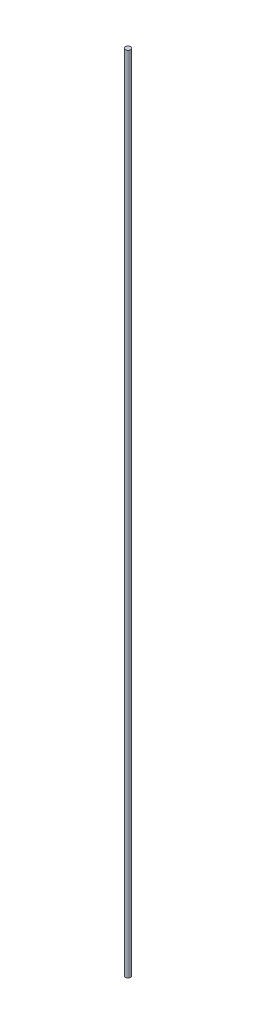
SolidWorks part; units mm, degrees
ref_plane "Спереди" through (0, 0, 0) normal (0, 0, 1) x (1, 0, 0)
ref_plane "Сверху" through (0, 0, 0) normal (0, 1, 0) x (1, 0, 0)
ref_plane "Справа" through (0, 0, 0) normal (1, 0, 0) x (0, 0, -1)
sketch "Эскиз2" plane through (0, 0, 0) normal (0, 0, 1) x (1, 0, 0)
  line L5 (-2.5, 380) -> (0, 380)
  line L6 (-2.5, 380) -> (-2.5, -380)
  line L7 (-2.5, -380) -> (0, -380)
  line L8 (0, 380) -> (0, -380)
  line L9 (-2.5, 380) -> (0, -380) construction
  line L10 (-2.5, -380) -> (0, 380) construction
  point P0 (-1.25, 0)
  point P5 (0, 0)
  dimension "D1" = 2.5
  dimension "D2" = 760
revolve "Повернуть1" add sketch "Эскиз2" angle 360 about L6
equation "\"Ширина груза\"= 420"
equation "\"Глубина груза\"= 490"
equation "\"Высота груза\"= 297"
equation "\"Ширина ячейки\"= \"Ширина груза\" + 10"
equation "\"Глубина ячейки\"= \"Глубина груза\" + 10"
equation "\"Высота ячейки\"= \"Высота груза\" + 10 + 13"
equation "\"Колво ячеек ширина\"= 2"
equation "\"Колво ячеек высота\"= 2"
equation "\"Толщина стенки\"= 10"
equation "\"Крепление дверцы\"= 5"
equation "\"Ширина рейки\"= \"Толщина шестерни\""
equation "\"Высота рейки\"= 20"
equation "\"Высота пола\"= 20"
equation "\"Колво полозьев\"= 5"
equation "\"Отступ рейки\"= 20"
equation "\"Глубина каретки\"= \"Глубина ячейки\" + 30 + \"Мотор Y высота корпуса\" + 20"
equation "\"Длинна рейки\"= ( \"Ширина ячейки\" + \"Толщина стенки\" + \"Крепление дверцы\" ) * \"Колво ячеек ширина\" + \"Ширина ячейки выгрузки\" * \"Колво выгрузки\" + \"Толщина стенки\""
equation "\"Отступ шпильки\"= 20"
equation "\"Диаметр шпильки\"= 5"
equation "\"Длинна шпильки\"= ( \"Высота ячейки\" + \"Толщина стенки\" + \"Высота пола\" ) * \"Колво ячеек высота\" + ( \"Толщина стенки\" + \"Отступ рейки\" ) * 2 "
equation "\"D1@Эскиз2\"= \"Диаметр шпильки\" / 2"
equation "\"D2@Эскиз2\"= \"Длинна шпильки\""
equation "\"Ширина пластины\"= 50  "
equation "\"Высота зона выгрузки\"= \"Высота ячейки\" * 2 + \"Толщина стенки\" * 2"
equation "\"Колво выгрузки\"= 1"
equation "\"Отступ крепления мотора фиксации\" = 30"
equation "\"Мотор X ширина корпуса\"= 42.3"
equation "\"Мотор X высота корпуса\"= 42.3"
equation "\"Мотор X длина корпуса\"= 40"
equation "\"Мотор X вылет вала\"= 19.8"
equation "\"Мотор Y ширина корпуса\"= 42.3"
equation "\"Мотор Y высота корпуса\"= 42.3"
equation "\"Мотор Y длина корпуса\"= 48"
equation "\"Мотор Y вылет вала\"= 30"
equation "\"Мотор Z ширина корпуса\"= 42"
equation "\"Мотор Z высота корпуса\"= 42"
equation "\"Мотор Z длина корпуса\"= 40"
equation "\"Мотор Z вылет вала\"= 23"
equation "\"Мотор диаметр вала ПРЕДВ\"= 5"
equation "\"Мотор шаг крепления ПРЕДВ\"= 31"
equation "\"Мотор диаметр отверстий ПРЕДВ\"= 3"
equation "\"Мотор глубина отверстий ПРЕДВ\"= 4.5"
equation "\"Мотор диаметр буртика ПРЕДВ\"= 22"
equation "\"Мотор высота буртика ПРЕДВ\"= 2"
equation "\"Мотор диаметр шкива ПРЕДВ\"= 16"
equation "\"Мотор длина шкива ПРЕДВ\"= 12"
equation "\"Мотор отступ шкива ПРЕДВ\"= 5"
equation "\"Мотор X шаг градусов\"= 1.8"
equation "\"Мотор X ток А\"= 1.5"
equation "\"Мотор X сопротивление Ом\"= 1.3"
equation "\"Мотор X индуктивность мГн\"= 2"
equation "\"Мотор Y шаг градусов\"= 1.8"
equation "\"Мотор Y ток А\"= 2.2"
equation "\"Мотор Y сопротивление Ом\"= 0.9"
equation "\"Мотор Y индуктивность мГн\"= 2"
equation "\"Мотор Z шаг градусов\"= 1.8"
equation "\"Мотор Z ток А\"= 1"
equation "\"Мотор Z сопротивление Ом\"= 4"
equation "\"Мотор Z индуктивность мГн\"= 8"
equation "\"Мотор Y диаметр ротора\"= 25.78"
equation "\"Ширина ячейки выгрузки\"= \"Ширина ячейки\" + \"Толщина стенки\" + \"Отступ крепления мотора фиксации\"*2"
